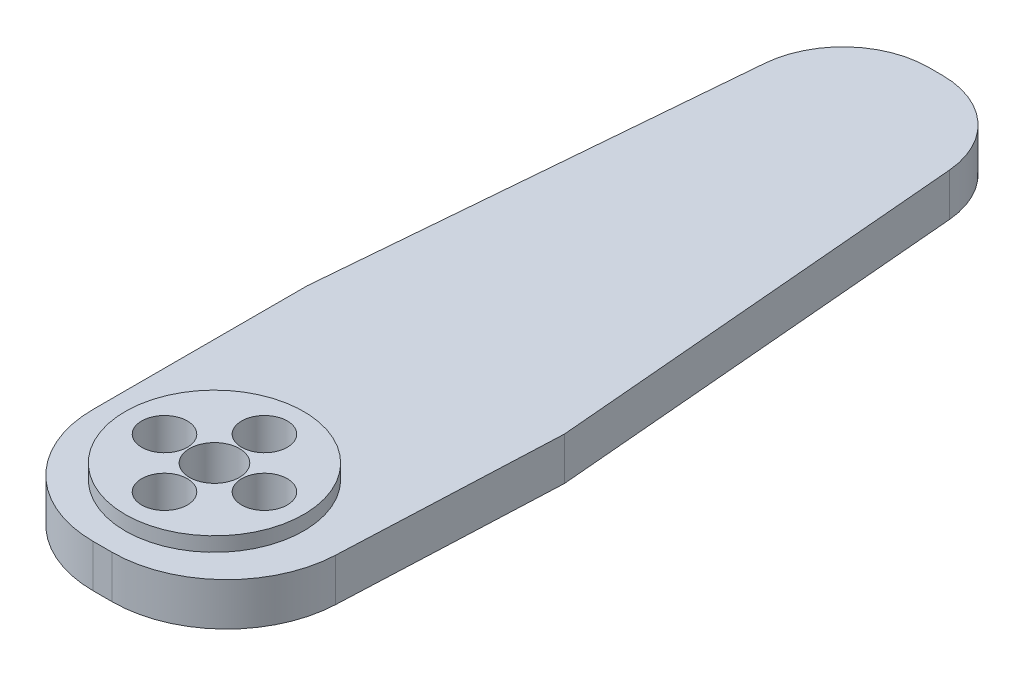
SolidWorks part; units mm, degrees
ref_plane "Front Plane" through (0, 0, 0) normal (0, 0, 1) x (1, 0, 0)
ref_plane "Top Plane" through (0, 0, 0) normal (0, 1, 0) x (1, 0, 0)
ref_plane "Right Plane" through (0, 0, 0) normal (1, 0, 0) x (0, 0, -1)
sketch "S_prism1" plane through (0, 0, 0) normal (0, 1, 0) x (1, 0, 0)
  line L0 (-1, -16) -> (1.6805, -16)
  line L1 (17.6654, -0.695) -> (19, 30)
  line L2 (19, 30) -> (13.9407, 89.0248)
  line L3 (1.9846, 100) -> (0.0154, 100)
  line L4 (-11.9407, 89.0248) -> (-17, 30)
  line L5 (-17, 30) -> (-17, 0)
  arc A0 (-17, 0) -> (-1, -16) centre (-1, 0) ccw
  arc A1 (1.6805, -16) -> (17.6654, -0.695) centre (1.6805, 0) ccw
  arc A2 (13.9407, 89.0248) -> (1.9846, 100) centre (1.9846, 88) ccw
  arc A3 (0.0154, 100) -> (-11.9407, 89.0248) centre (0.0154, 88) ccw
extrude "Boss_1" add sketch "S_prism1" along normal blind 6
ref_plane "PY_p6_000" through (0, 6, 0) normal (0, 1, 0) x (1, 0, 0)
sketch "S_cyl2" plane through (0, 6, 0) normal (0, 1, 0) x (1, 0, 0)
  circle A0 centre (0, 0) radius 12.5
  dimension "D1_S_cyl2" = 25
extrude "Boss_2" add sketch "S_cyl2" along normal blind 2
ref_plane "PY_m0_100" through (0, -0.1, 0) normal (0, 1, 0) x (1, 0, 0)
sketch "S_hole3" plane through (0, -0.1, 0) normal (0, 1, 0) x (1, 0, 0)
  circle A0 centre (0, 0) radius 3.5
  dimension "D1_S_hole3" = 7
extrude "Hole_3" cut sketch "S_hole3" along normal blind 8.2
sketch "S_hole4" plane through (0, -0.1, 0) normal (0, 1, 0) x (1, 0, 0)
  circle A0 centre (7, 0) radius 1.7
  dimension "D1_S_hole4" = 3.4
  dimension "P2" = 7
extrude "Hole_4" cut sketch "S_hole4" along normal blind 8.2
sketch "S_hole5" plane through (0, -0.1, 0) normal (0, 1, 0) x (1, 0, 0)
  circle A0 centre (0, -7) radius 1.7
  dimension "D1_S_hole5" = 3.4
  dimension "P2" = 7
extrude "Hole_5" cut sketch "S_hole5" along normal blind 8.2
sketch "S_hole6" plane through (0, -0.1, 0) normal (0, 1, 0) x (1, 0, 0)
  circle A0 centre (-7, 0) radius 1.7
  dimension "D1_S_hole6" = 3.4
  dimension "P2" = 7
extrude "Hole_6" cut sketch "S_hole6" along normal blind 8.2
sketch "S_hole7" plane through (0, -0.1, 0) normal (0, 1, 0) x (1, 0, 0)
  circle A0 centre (0, 7) radius 1.7
  dimension "D1_S_hole7" = 3.4
  dimension "P2" = 7
extrude "Hole_7" cut sketch "S_hole7" along normal blind 8.2
ref_plane "PY_p3_000" through (0, 3, 0) normal (0, 1, 0) x (1, 0, 0)
sketch "S_hole8" plane through (0, 3, 0) normal (0, 1, 0) x (1, 0, 0)
  circle A0 centre (7, 0) radius 3.2
  dimension "D1_S_hole8" = 6.4
  dimension "P2" = 7
extrude "Hole_8" cut sketch "S_hole8" along normal blind 5.1
sketch "S_hole9" plane through (0, 3, 0) normal (0, 1, 0) x (1, 0, 0)
  circle A0 centre (0, -7) radius 3.2
  dimension "D1_S_hole9" = 6.4
  dimension "P2" = 7
extrude "Hole_9" cut sketch "S_hole9" along normal blind 5.1
sketch "S_hole10" plane through (0, 3, 0) normal (0, 1, 0) x (1, 0, 0)
  circle A0 centre (-7, 0) radius 3.2
  dimension "D1_S_hole10" = 6.4
  dimension "P2" = 7
extrude "Hole_10" cut sketch "S_hole10" along normal blind 5.1
sketch "S_hole11" plane through (0, 3, 0) normal (0, 1, 0) x (1, 0, 0)
  circle A0 centre (0, 7) radius 3.2
  dimension "D1_S_hole11" = 6.4
  dimension "P2" = 7
extrude "Hole_11" cut sketch "S_hole11" along normal blind 5.1
equation "\"plate_t\" = 3"
equation "\"clearance\" = 0.5"
